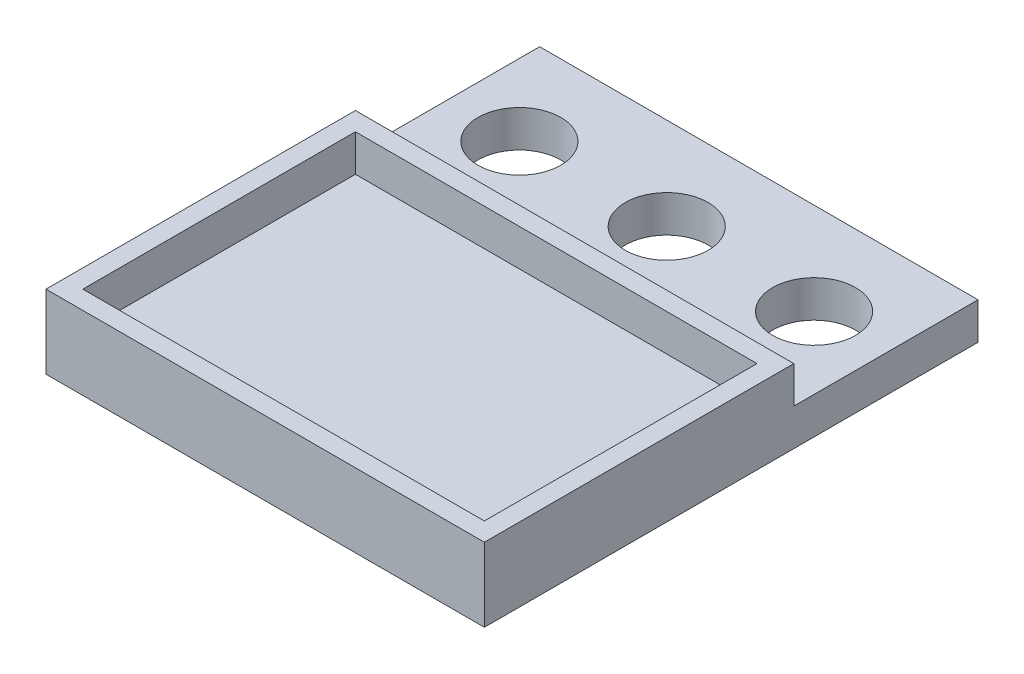
SolidWorks part; units mm, degrees
ref_plane "前视基准面" through (0, 0, 0) normal (0, 0, 1) x (1, 0, 0)
ref_plane "上视基准面" through (0, 0, 0) normal (0, 1, 0) x (1, 0, 0)
ref_plane "右视基准面" through (0, 0, 0) normal (1, 0, 0) x (0, 0, -1)
sketch "草图1" plane through (0, 0, 0) normal (0, 1, 0) x (1, 0, 0)
  line L0 (0, -18.0344) -> (0, 18.0344) construction
  line L1 (-10.9, 7.4) -> (10.9, 7.4)
  line L2 (-10.9, 7.4) -> (-10.9, -7.4)
  line L3 (-10.9, -7.4) -> (10.9, -7.4)
  line L4 (10.9, 7.4) -> (10.9, -7.4)
  line L5 (-10.9, 7.4) -> (10.9, -7.4) construction
  line L6 (-10.9, -7.4) -> (10.9, 7.4) construction
  line L7 (-11.9, 8.4) -> (11.9, 8.4)
  line L8 (-11.9, 8.4) -> (-11.9, -8.4)
  line L9 (-11.9, -8.4) -> (11.9, -8.4)
  line L10 (11.9, 8.4) -> (11.9, -8.4)
  line L11 (-11.9, 8.4) -> (11.9, -8.4) construction
  line L12 (-11.9, -8.4) -> (11.9, 8.4) construction
  line L13 (-11.9, 8.4) -> (11.9, 8.4)
  line L14 (-11.9, 8.4) -> (-11.9, 18.4)
  line L15 (-11.9, 18.4) -> (11.9, 18.4)
  line L16 (11.9, 8.4) -> (11.9, 18.4)
  circle A0 centre (0, 13.4) radius 2.25
  circle A1 centre (-8, 13.4) radius 2.25
  circle A3 centre (8, 13.4) radius 2.25
  point P0 (0, 0)
  point P6 (0, 0)
  point P15 (0, 0)
  point P18 (-5.9816, 13.8886)
  point P21 (5.6689, 13.8886)
  point P24 (0, 0)
  point P25 (-11.9, 13.4)
  dimension "D6" = 4.5
  dimension "D8" = 4.5
  dimension "D1" = 21.8
  dimension "D2" = 14.8
  dimension "D3" = 1
  dimension "D4" = 1
  dimension "D5" = 10
  dimension "D7" = 8
extrude "凸台-拉伸1" add sketch "草图1" along normal blind 2 contours L7 L16 L15 L14 A0 A1 A3 | L10 L7 L8 L9 L1 L4 L3 L2 | L4 L1 L2 L3 region at (0, 0, 0) region at (-11.6418, 0, -13.4) region at (0, 0, -8.1087)
extrude "凸台-拉伸2" add sketch "草图1<3>" along normal blind 2 from surface contours L10 L7 L8 L9 L1 L4 L3 L2 region at (0, 0, -8.1087) starting at face at (0, 2, -5)
sketch "草图1<3>" plane through (0, 0, 0) normal (0, 1, 0) x (1, 0, 0) same geometry as "草图1"
